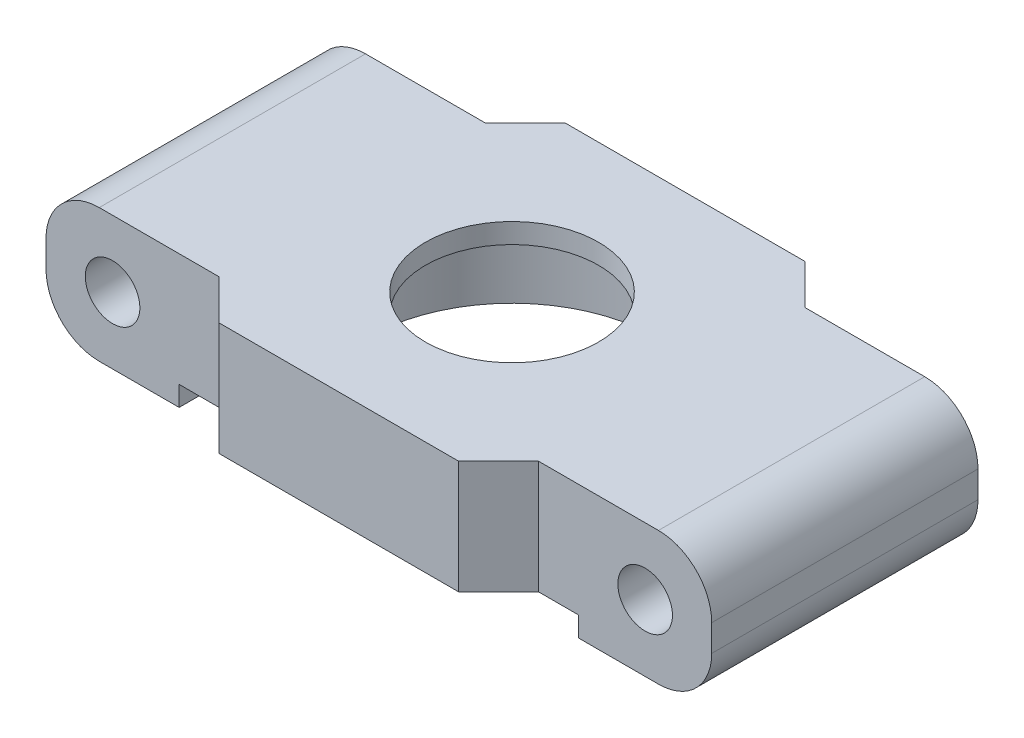
SolidWorks part; units mm, degrees
ref_plane "Front Plane" through (0, 0, 0) normal (0, 0, 1) x (1, 0, 0)
ref_plane "Top Plane" through (0, 0, 0) normal (0, 1, 0) x (1, 0, 0)
ref_plane "Right Plane" through (0, 0, 0) normal (1, 0, 0) x (0, 0, -1)
sketch "Sketch1" plane through (0, 0, 0) normal (0, 1, 0) x (1, 0, 0)
  line L0 (-15, 10) -> (-25, 10)
  line L1 (-15, 13) -> (15, 13)
  line L2 (-15, 13) -> (-15, -13)
  line L3 (-15, -13) -> (15, -13)
  line L4 (15, 13) -> (15, -13)
  line L5 (-15, 13) -> (15, -13) construction
  line L6 (-15, -13) -> (15, 13) construction
  line L7 (-25, 10) -> (-25, -10)
  line L8 (-25, -10) -> (-15, -10)
  line L9 (15, 10) -> (25, 10)
  line L10 (25, 10) -> (25, -10)
  line L11 (25, -10) -> (15, -10)
  circle A0 centre (0, 0) radius 11
  point P0 (0, 0)
  point P16 (-25, 0)
  point P17 (25, 0)
  dimension "D2" = 22
  dimension "D1" = 20
  dimension "D3" = 10
  dimension "D4" = 30
  dimension "D5" = 26
extrude "Boss-Extrude1" add sketch "Sketch1" along normal mid plane 7 contours L4 L1 L2 L3 A0 region at (-14.603, 0, -11.5)
extrude "Boss-Extrude2" add sketch "Sketch1<3>" along normal mid plane 10 contours L7 L8 L2 L0 | L11 L10 L9 L4 region at (-20, 0, 0) region at (20, 0, 0)
sketch "Sketch1<3>" plane through (0, 0, 0) normal (0, 1, 0) x (1, 0, 0) same geometry as "Sketch1"
sketch "Sketch2" plane through (0, 0, -10) normal (0, 0, -1) x (-1, 0, 0)
  line L1 (-15, 5) -> (-25, 5) construction
  line L2 (15, 5) -> (25, 5) construction
  circle A0 centre (-20, 0) radius 2.05
  circle A1 centre (20, 0) radius 2.05
  point P7 (-20, 5)
  point P11 (20, 5)
  dimension "D1" = 4.1
extrude "Cut-Extrude1" cut sketch "Sketch2" against normal blind 30
fillet "Fillet1" radius 4 4 edges at (25, -5, 0) (25, 5, 0) (-25, -5, 0) (-25, 5, 0)
chamfer "Chamfer1" distance 6 angle 45 4 edges at (15, 0, -13) (15, 0, 13) (-15, 0, 13) (-15, 0, -13)
sketch "Sketch3" plane through (0, 3.5, 0) normal (0, 1, 0) x (1, 0, 0)
  line L12 (15, -10) -> (15, 10)
  line L13 (15, 10) -> (12, 10)
  line L14 (12, 10) -> (9, 13)
  line L15 (9, 13) -> (-9, 13)
  line L16 (-9, 13) -> (-12, 10)
  line L17 (-12, 10) -> (-15, 10)
  line L18 (-15, 10) -> (-15, -10)
  line L19 (-15, -10) -> (-12, -10)
  line L20 (-12, -10) -> (-9, -13)
  line L21 (-9, -13) -> (9, -13)
  line L22 (9, -13) -> (12, -10)
  line L23 (12, -10) -> (15, -10)
  line L24 (15, -10) -> (15, 10)
  line L25 (15, 10) -> (12, 10)
  line L26 (12, 10) -> (9, 13)
  line L27 (9, 13) -> (-9, 13)
  line L28 (-9, 13) -> (-12, 10)
  line L29 (-12, 10) -> (-15, 10)
  line L30 (-15, 10) -> (-15, -10)
  line L31 (-15, -10) -> (-12, -10)
  line L32 (-12, -10) -> (-9, -13)
  line L33 (-9, -13) -> (9, -13)
  line L34 (9, -13) -> (12, -10)
  line L35 (12, -10) -> (15, -10)
  circle A0 centre (0, 0) radius 6.5
  dimension "D2" = 13
  dimension "D1" = 0
extrude "Boss-Extrude3" add sketch "Sketch3" along normal up to surface (1.5 mm away) up to face at (18, 5, 0)
